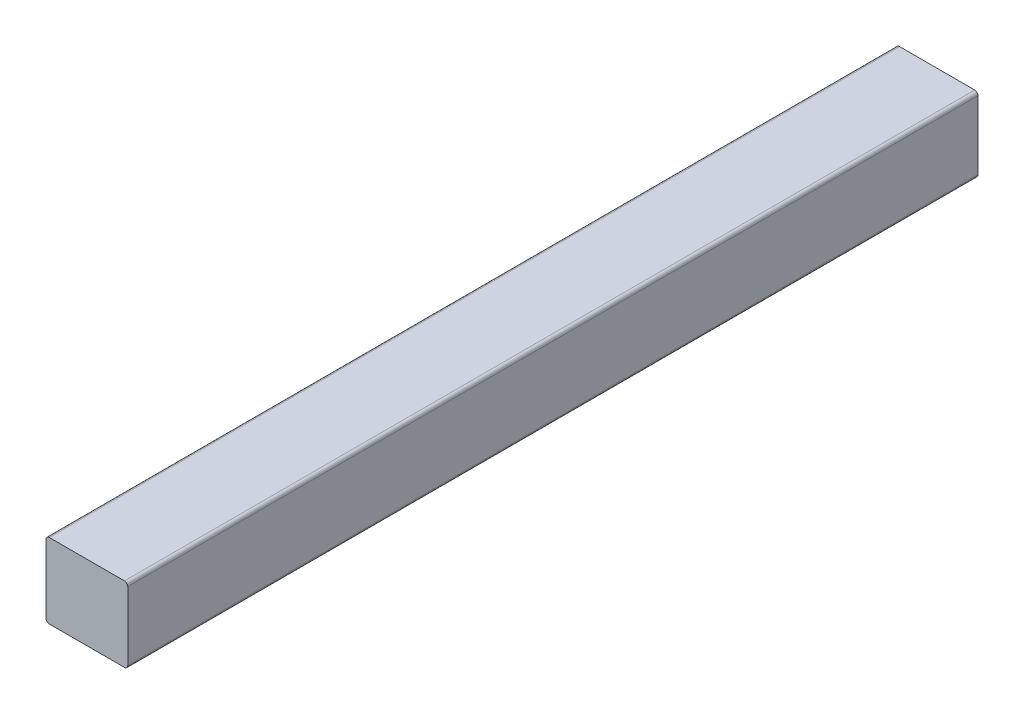
SolidWorks part; units mm, degrees
material "Plain Carbon Steel"
ref_plane "Front Plane" through (0, 0, 0) normal (0, 0, 1) x (1, 0, 0)
ref_plane "Top Plane" through (0, 0, 0) normal (0, 1, 0) x (1, 0, 0)
ref_plane "Right Plane" through (0, 0, 0) normal (1, 0, 0) x (0, 0, -1)
sketch "Sketch1" plane through (0, 0, 0) normal (0, 0, 1) x (1, 0, 0)
  line L0 (50, 2) -> (50, 0) construction
  line L1 (2, 0) -> (48, 0)
  line L2 (0, 2) -> (0, 43.8258)
  line L3 (2, 45.8258) -> (48, 45.8258)
  line L4 (50, 2) -> (50, 43.8258)
  line L5 (50, 0) -> (48, 0) construction
  line L6 (0, 2) -> (0, 0) construction
  line L7 (0, 0) -> (2, 0) construction
  line L9 (-250, 0) -> (50, 0) construction
  arc A0 (2, 0) -> (0, 2) centre (2, 2) cw
  arc A1 (48, 0) -> (50, 2) centre (48, 2) ccw
  arc A2 (48, 45.8258) -> (50, 43.8258) centre (48, 43.8258) cw
  arc A3 (0, 43.8258) -> (2, 45.8258) centre (2, 43.8258) cw
  point P7 (50, 0)
  point P12 (50, 45.8258)
  point P15 (0, 45.8258)
  point P16 (0, 0)
  dimension "D3" = 2
  dimension "D2" = 50
extrude "Boss-Extrude1" add sketch "Sketch1" along normal blind 520
sketch "Center_lines" plane through (0, 45.8258, 0) normal (0, 1, 0) x (1, 0, 0)
  line L0 (25, 58.7626) -> (25, -578.7626) construction
  line L1 (0, -260) -> (50, -260) construction
  line L2 (48, 0) -> (2, 0) construction
  line L3 (48, -520) -> (48, 0) construction
  line L4 (0, -520) -> (0, 0) construction
  point P6 (25, 0)
  point P7 (25, -260)
  point P10 (48, -260)
  point P15 (25, -260)
sketch "Tube_end_reference" plane through (0, 0, 520) normal (0, 0, 1) x (1, 0, 0)
  line L0 (50, 2) -> (50, 43.8258) construction
  line L1 (50, 45.8258) -> (0, 45.8258) construction
  line L2 (50, 45.8258) -> (50, 0) construction
  line L3 (50, 0) -> (0, 0) construction
  line L4 (0, 45.8258) -> (0, 0) construction
  line L5 (0, 43.8258) -> (0, 2) construction
  line L6 (0, 45.8258) -> (50, 45.8258) construction
  line L7 (2, 0) -> (48, 0) construction
sketch "Tube_corners_R" plane through (50, 0, 0) normal (1, 0, 0) x (0, 0, -1)
  line L0 (-520, 0) -> (0, 0) construction
  line L1 (-520, 45.8258) -> (0, 45.8258) construction
sketch "Tube_corners_L" plane through (0, 0, 0) normal (-1, 0, 0) x (0, 0, 1)
  line L0 (520, 45.8258) -> (0, 45.8258) construction
  line L1 (520, 0) -> (0, 0) construction
